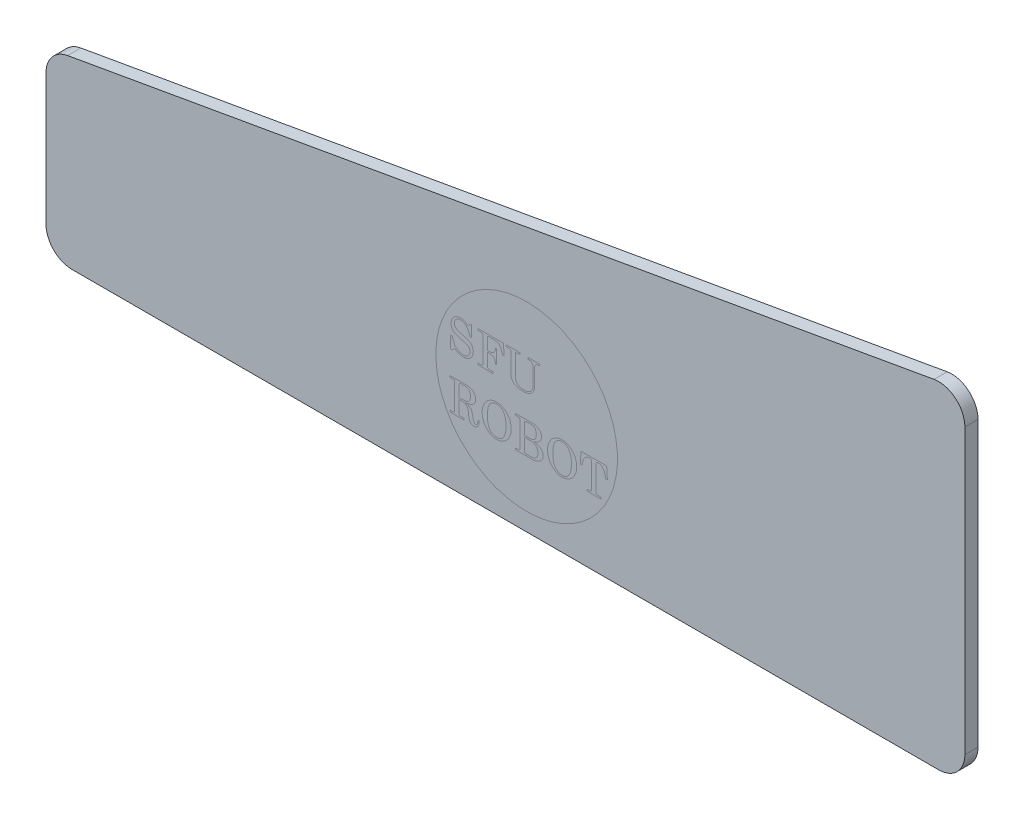
SolidWorks part; units mm, degrees
material "Acrylic (Medium-high impact)"
ref_plane "Front Plane" through (0, 0, 0) normal (0, 0, 1) x (1, 0, 0)
ref_plane "Top Plane" through (0, 0, 0) normal (0, 1, 0) x (1, 0, 0)
ref_plane "Right Plane" through (0, 0, 0) normal (1, 0, 0) x (0, 0, -1)
sketch "Sketch1" plane through (0, 0, 0) normal (0, 0, 1) x (1, 0, 0)
  line L0 (0, 0) -> (-350, 0)
  line L1 (-350, 0) -> (-350, 68.2856)
  line L2 (-350, 68.2856) -> (0, 130)
  line L3 (0, 130) -> (0, 0)
  dimension "D1" = 350
  dimension "D2" = 10
  dimension "D3" = 130
extrude "Boss-Extrude1" add sketch "Sketch1" along normal blind 5
fillet "Fillet1" [suppressed] radius 10
fillet "Fillet2" radius 10 4 edges at (0, 0, 2.5) (-350, 0, 2.5) (-350, 68.2856, 2.5) (0, 130, 2.5)
sketch "Sketch4" plane through (0, 0, 5) normal (0, 0, 1) x (1, 0, 0)
  text T0 "SFU\r\nROBOT" font "Century Schoolbook" height 12
wrap "Wrap1" sketch "Sketch4" wrap type scribe source sketch "Sketch4" face at (-175.3711, 49.4685, 5)
sketch "Sketch5" plane through (0, 0, 5) normal (0, 0, 1) x (1, 0, 0)
  circle A0 centre (-166.9149, 41.3545) radius 34.5987
wrap "Wrap2" sketch "Sketch5" wrap type scribe source sketch "Sketch5" face at (-175.3711, 49.4685, 5)
